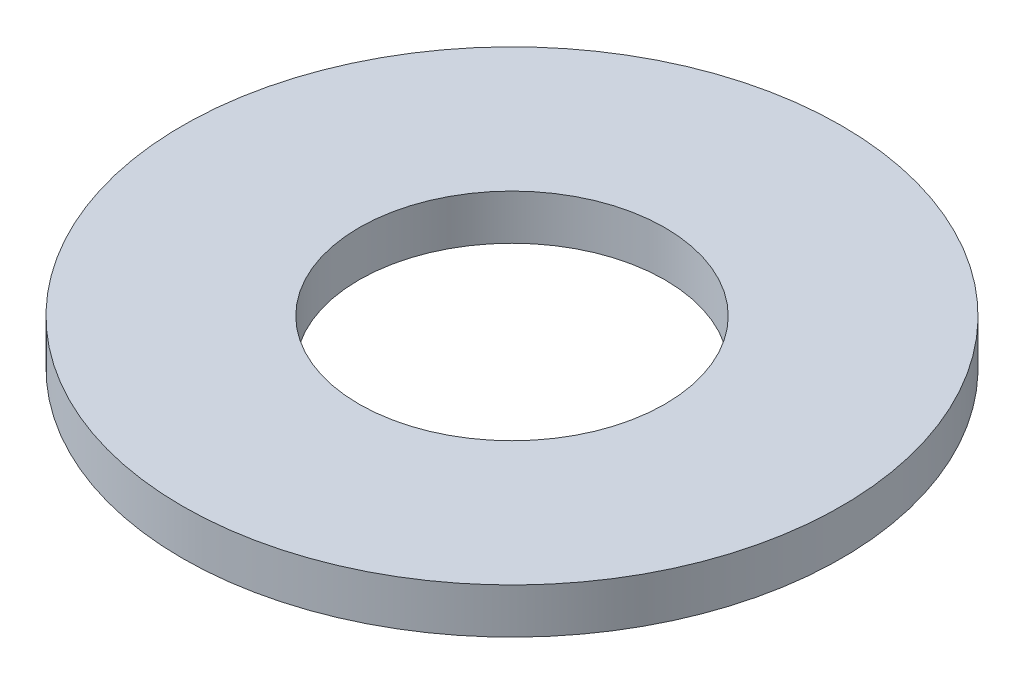
SolidWorks part; units mm, degrees
material "AISI 4130 Steel, normalized at 870C"
ref_plane "Front Plane" through (0, 0, 0) normal (0, 0, 1) x (1, 0, 0)
ref_plane "Top Plane" through (0, 0, 0) normal (0, 1, 0) x (1, 0, 0)
ref_plane "Right Plane" through (0, 0, 0) normal (1, 0, 0) x (0, 0, -1)
sketch "Sketch1" plane through (0, 0, 0) normal (0, 1, 0) x (1, 0, 0)
  circle A0 centre (0, 0) radius 11.1125
  dimension "OD" = 22.225
extrude "Boss-Extrude1" add sketch "Sketch1" along normal blind 1.524
sketch "Sketch5" plane through (0, 1.524, 0) normal (0, 1, 0) x (-1, 0, 0)
  circle A0 centre (0, 0) radius 5.1562
  dimension "ID" = 10.3124
extrude "Cut-Extrude1" cut sketch "Sketch5" against normal through all
move or copy body "Body-Move/Copy1" [suppressed] bodies to move or copy 103 parameters "D1"=0, "D2"=0, "D3"=0
move or copy body "Body-Move/Copy2" [suppressed] bodies to move or copy 104 parameters "D1"=0, "D2"=0, "D3"=0
move or copy body "Body-Move/Copy3" [suppressed] bodies to move or copy 105 parameters "D1"=0, "D2"=0, "D3"=0
move or copy body "Body-Move/Copy4" [suppressed] bodies to move or copy 106 parameters "D1"=0, "D2"=0, "D3"=0
move or copy body "Body-Move/Copy5" [suppressed] bodies to move or copy 107 parameters "D1"=0, "D2"=0, "D3"=0
move or copy body "Body-Move/Copy6" [suppressed] bodies to move or copy 108 parameters "D1"=0, "D2"=0, "D3"=0
move or copy body "Body-Move/Copy7" [suppressed] bodies to move or copy 109 parameters "D1"=0, "D2"=0, "D3"=0
move or copy body "Body-Move/Copy8" [suppressed] bodies to move or copy 110 parameters "D1"=0, "D2"=0, "D3"=0
